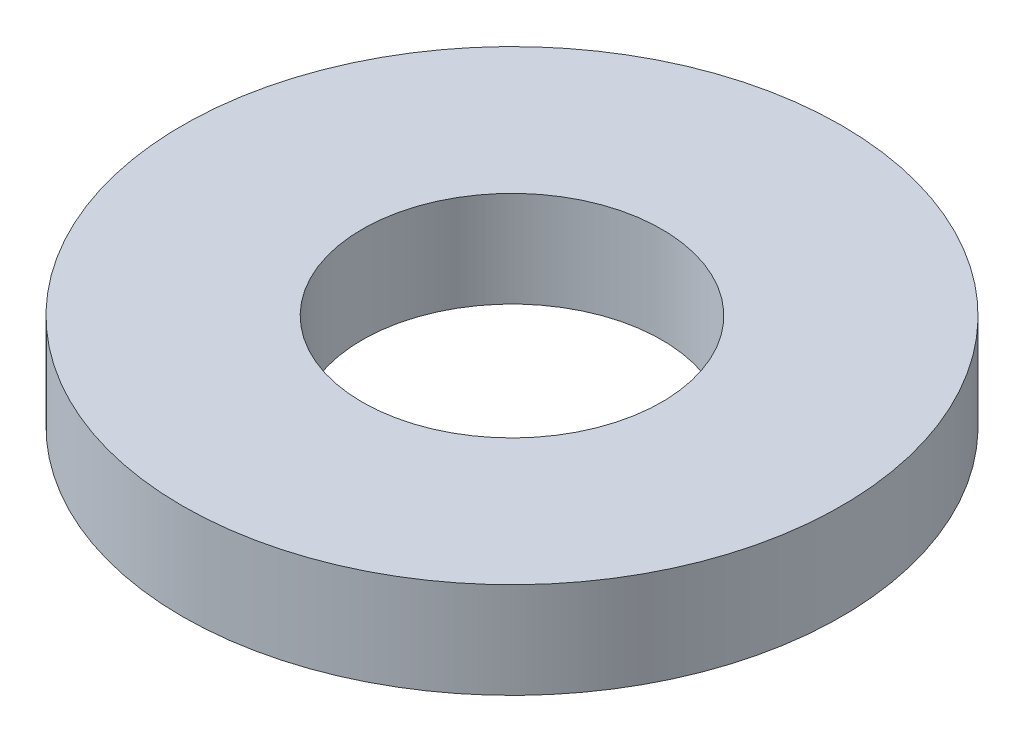
SolidWorks part; units mm, degrees
ref_plane "Front Plane" through (0, 0, 0) normal (0, 0, 1) x (1, 0, 0)
ref_plane "Top Plane" through (0, 0, 0) normal (0, 1, 0) x (1, 0, 0)
ref_plane "Right Plane" through (0, 0, 0) normal (1, 0, 0) x (0, 0, -1)
sketch "Sketch1" plane through (0, 0, 0) normal (0, 1, 0) x (1, 0, 0)
  circle A0 centre (0, 0) radius 82.5
  dimension "FLANGE_OD" = 165
extrude "Boss-Extrude1" add sketch "Sketch1" along normal blind 24
sketch "Sketch2" plane through (0, 0, 0) normal (0, 1, 0) x (1, 0, 0)
  circle A0 centre (0, 0) radius 37.5
  dimension "BORE_D" = 75
extrude "Cut-Extrude1" cut sketch "Sketch2" along normal through all
sketch "Sketch3" plane through (0, 24, 0) normal (0, 1, 0) x (1, 0, 0)
  circle A0 centre (0, 0) radius 27.4067 construction
  circle A1 centre (-27.4067, 0) radius 2.3246
  dimension "BOLT_D" = 4.6492
  dimension "BOLT_PCD" = 54.8134
extrude "Cut-Extrude2" cut sketch "Sketch3" against normal blind 15.9111 rebuild error yes
pattern_circular "CirPattern1" count 3 over 360 rebuild error yes
